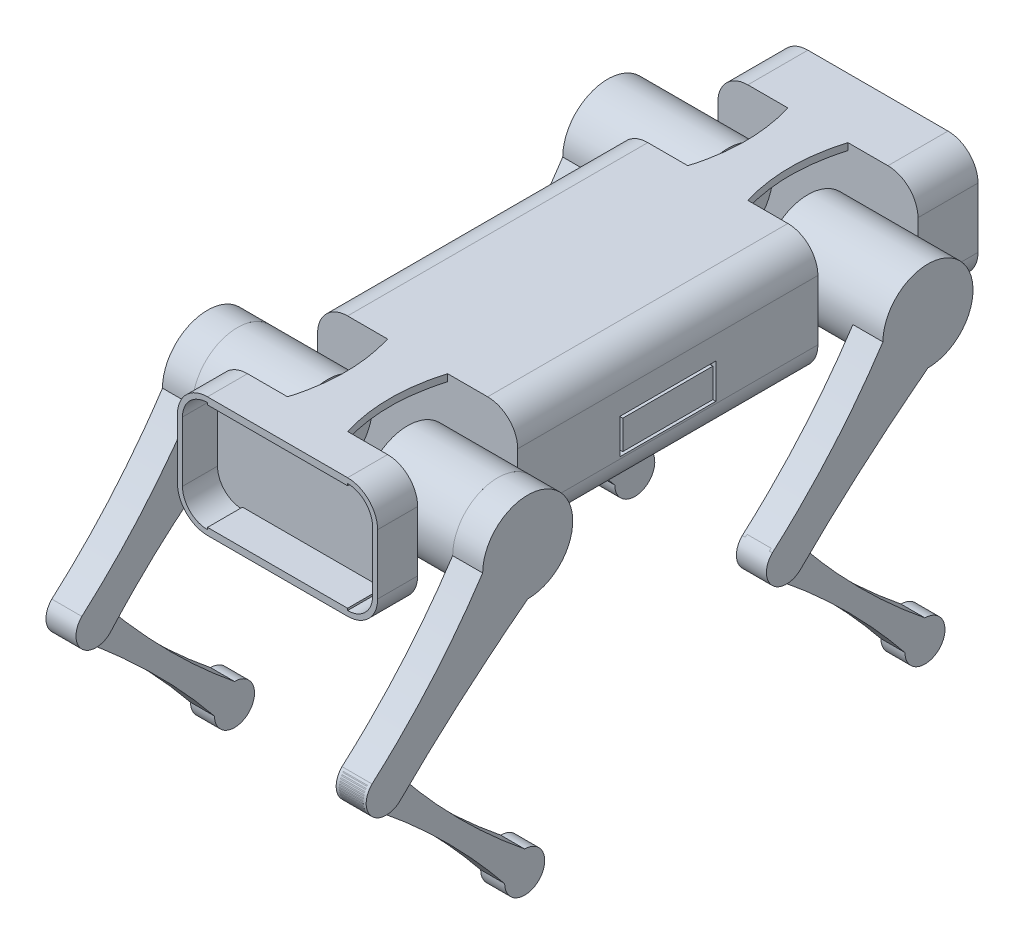
SolidWorks part; units mm, degrees
note: The reader was unsure of these and kept them because the rebuilt part matched: shared geometry of "草图12<2>", "草图13<2>".
ref_plane "前视基准面" through (0, 0, 0) normal (0, 0, 1) x (1, 0, 0)
ref_plane "上视基准面" through (0, 0, 0) normal (0, 1, 0) x (1, 0, 0)
ref_plane "右视基准面" through (0, 0, 0) normal (1, 0, 0) x (0, 0, -1)
sketch "草图1" plane through (0, 0, 0) normal (0, 0, 1) x (1, 0, 0)
  line L0 (-100, 30) -> (-100, -30)
  line L1 (-70, -60) -> (70, -60)
  line L6 (100, 30) -> (100, -30)
  line L7 (70, 60) -> (-70, 60)
  arc A0 (-70, 60) -> (-100, 30) centre (-70, 30) ccw
  arc A1 (-70, -60) -> (-100, -30) centre (-70, -30) cw
  arc A2 (100, -30) -> (70, -60) centre (70, -30) cw
  arc A3 (100, 30) -> (70, 60) centre (70, 30) ccw
extrude "机身" add sketch "草图1" along normal blind 300
ref_plane "基准面4" through (0, 0, 0) normal (-1, 0, 0) x (0, 0, 1)
sketch "草图3" plane through (0, 0, 0) normal (-1, 0, 0) x (0, 0, 1)
  circle A0 centre (-50, 0) radius 45
  circle A2 centre (350, 0) radius 45
extrude "髋部" add sketch "草图3" along normal mid plane 260 separate body
sketch "草图6" plane through (0, 0, 0) normal (-1, 0, 0) x (0, 0, 1)
  circle A0 centre (-50, 0) radius 45
  circle A1 centre (350, 0) radius 45
extrude "髋部切1" cut sketch "草图6" against normal mid plane 80
ref_plane "基准面5" through (-130, 0, 0) normal (-1, 0, 0) x (0, 0, 1)
sketch "草图7" plane through (-130, 0, 0) normal (-1, 0, 0) x (0, 0, 1)
  circle A0 centre (-50, 0) radius 45 construction
  arc A1 (77.2792, -155.5635) -> (105.5635, -127.2792) centre (91.4214, -141.4214) ccw
  arc A2 (-50, -45) -> (-5, 0) centre (-50, 0) cw
  arc A5 (477.2792, -155.5635) -> (505.5635, -127.2792) centre (491.4214, -141.4214) ccw [skipped]
  arc A6 (350, -45) -> (395, 0) centre (350, 0) cw [skipped]
  arc A7 (477.2792, -155.5635) -> (505.5635, -127.2792) centre (491.4214, -141.4214) ccw
  arc A8 (350, -45) -> (395, 0) centre (350, 0) cw
  spline S0 degree 2 poles (-50, -45) (21.0347, -91.8313) (77.2792, -155.5635) knots 0 0 0 1 1 1
  spline S1 degree 2 poles (-5, 0) (41.8313, -71.0347) (105.5635, -127.2792) knots 0 0 0 1 1 1
  spline S2 degree 2 poles (350, -45) (421.0347, -91.8313) (477.2792, -155.5635) knots 0 0 0 1 1 1
  spline S3 degree 2 poles (395, 0) (441.8313, -71.0347) (505.5635, -127.2792) knots 0 0 0 1 1 1
  dimension "D1" = 2
extrude "左大腿" add sketch "草图7" along normal blind 30
ref_plane "基准面6" through (130, 0, 0) normal (1, 0, 0) x (0, 0, -1)
sketch "草图8" plane through (130, 0, 0) normal (1, 0, 0) x (0, 0, -1)
  line L0 (-350, -45) -> (-420.8207, -99.105) construction
  line L1 (-420.8207, -99.105) -> (-477.2792, -155.5635) construction
  line L3 (50, -45) -> (-20.8207, -99.105) construction
  line L4 (-20.8207, -99.105) -> (-77.2792, -155.5635) construction
  arc A5 (-395, 0) -> (-350, -45) centre (-350, 0) cw
  arc A6 (-477.2792, -155.5635) -> (-505.5635, -127.2792) centre (-491.4214, -141.4214) cw
  arc A9 (5, 0) -> (50, -45) centre (50, 0) cw
  circle A10 centre (50, 0) radius 45 construction
  arc A11 (-77.2792, -155.5635) -> (-105.5635, -127.2792) centre (-91.4214, -141.4214) cw
  parabola Q0 (-105.5635, -127.2792) -> (5, 0) focus (-285.6819, 139.285) apex (-47.5776, -69.0817) construction
  spline S0 degree 2 poles (50, -45) (-20.8207, -99.105) (-77.2792, -155.5635) knots 0 0 0 1 1 1
  spline S1 degree 2 poles (5, 0) (-41.8313, -71.0347) (-105.5635, -127.2792) knots 0 0 0 1 1 1
  spline S2 degree 2 poles (-350, -45) (-420.8207, -99.105) (-477.2792, -155.5635) knots 0 0 0 1 1 1
  spline S3 degree 2 poles (-395, 0) (-441.8313, -71.0347) (-505.5635, -127.2792) knots 0 0 0 1 1 1
  dimension "D1" = 2
extrude "右大腿" add sketch "草图8" along normal blind 30
ref_plane "基准面7" through (0, 60, 0) normal (0, 1, 0) x (1, 0, 0)
sketch "草图10" plane through (0, 60, 0) normal (0, 1, 0) x (1, 0, 0)
  line L1 (70, 100) -> (30, 100)
  line L7 (70, -400) -> (70, -440)
  line L9 (70, -400) -> (30, -400)
  line L12 (30, -400) -> (15, -350) construction
  line L13 (15, -350) -> (30, -300) construction
  line L14 (-30, -400) -> (-15, -350) construction
  line L15 (-15, -350) -> (-30, -300) construction
  line L16 (30, -300) -> (-30, -300)
  line L19 (70, 0) -> (-70, 0) construction
  line L20 (-30, 0) -> (30, 0)
  line L25 (-70, 160) -> (-70, 100)
  line L26 (70, 160) -> (70, 100)
  line L27 (-30, 100) -> (-15, 50) construction
  line L28 (-15, 50) -> (-30, 0) construction
  line L29 (30, 100) -> (15, 50) construction
  line L30 (15, 50) -> (30, 0) construction
  line L31 (-30, 100) -> (-70, 100)
  line L32 (-70, 160) -> (70, 160)
  line L33 (70, -440) -> (-70, -440)
  line L34 (-30, -400) -> (-70, -400)
  line L35 (-70, -400) -> (-70, -440)
  spline S0 degree 2 poles (30, -400) (15, -350) (30, -300) knots 0 0 0 1 1 1
  spline S1 degree 2 poles (-30, -400) (-15, -350) (-30, -300) knots 0 0 0 1 1 1
  spline S2 degree 2 poles (-30, 100) (-15, 50) (-30, 0) knots 0 0 0 1 1 1
  spline S3 degree 2 poles (30, 100) (15, 50) (30, 0) knots 0 0 0 1 1 1
extrude "上机架" add sketch "草图10" against normal blind 7 separate body
ref_plane "基准面8" through (0, -60, 0) normal (0, -1, 0) x (-1, 0, 0)
sketch "草图11" plane through (0, -60, 0) normal (0, -1, 0) x (-1, 0, 0)
  line L0 (-30, 100) -> (-70, 100)
  line L1 (-70, 100) -> (-70, 160)
  line L2 (-70, 160) -> (70, 160)
  line L3 (70, 160) -> (70, 100)
  line L4 (70, 100) -> (30, 100)
  line L5 (-70, -440) -> (70, -440)
  line L6 (70, -440) -> (70, -400)
  line L7 (70, -400) -> (30, -400)
  line L8 (-30, 100) -> (-11.25, 50) construction
  line L9 (-11.25, 50) -> (-30, 0) construction
  line L12 (30, 100) -> (11.25, 50) construction
  line L13 (11.25, 50) -> (30, 0) construction
  line L16 (-30, 0) -> (30, 0)
  line L17 (-30, -400) -> (-70, -400)
  line L18 (-70, -400) -> (-70, -440)
  line L24 (-30, -300) -> (-11.25, -350) construction
  line L25 (-11.25, -350) -> (-30, -400) construction
  line L28 (30, -300) -> (11.25, -350) construction
  line L29 (11.25, -350) -> (30, -400) construction
  line L30 (-30, -300) -> (30, -300)
  spline S0 degree 2 poles (-30, 100) (-11.25, 50) (-30, 0) knots 0 0 0 1 1 1
  spline S1 degree 2 poles (30, 100) (11.25, 50) (30, 0) knots 0 0 0 1 1 1
  spline S2 degree 2 poles (-30, -300) (-11.25, -350) (-30, -400) knots 0 0 0 1 1 1
  spline S3 degree 2 poles (30, -300) (11.25, -350) (30, -400) knots 0 0 0 1 1 1
extrude "下机架" add sketch "草图11" against normal blind 7
ref_plane "基准面9" through (0, 0, -100) normal (0, 0, 1) x (1, 0, 0)
sketch "草图12" plane through (0, 0, -100) normal (0, 0, 1) x (1, 0, 0)
  line L0 (-70, -60) -> (70, -60)
  line L1 (-77, -60) -> (77, -60) construction
  line L3 (70, 60) -> (-70, 60)
  line L4 (70, 60) -> (-70, 60) construction
  line L5 (77, 60) -> (-77, 60) construction
  line L7 (-100, 30) -> (-100, -30)
  line L9 (100, 30) -> (100, -30)
  arc A0 (-100, -30) -> (-70, -60) centre (-70, -30) ccw construction
  arc A1 (70, -60) -> (100, -30) centre (70, -30) ccw construction
  arc A2 (70, -60) -> (100, -30) centre (70, -30) ccw
  arc A3 (70, 60) -> (100, 30) centre (70, 30) cw
  arc A4 (100, 30) -> (70, 60) centre (70, 30) ccw construction
  arc A5 (-70, 60) -> (-100, 30) centre (-70, 30) ccw
  arc A6 (-70, 60) -> (-100, 30) centre (-70, 30) ccw construction
  arc A7 (-70, -60) -> (-100, -30) centre (-70, -30) cw
extrude "头" add sketch "草图12" against normal blind 5
extrude "头框" add sketch "草图12<2>" against normal blind 60 thin thin type one direction reverse wall 5
sketch "草图12<2>" plane through (0, 0, -100) normal (0, 0, 1) x (1, 0, 0) same geometry as "草图12"
ref_plane "基准面10" through (0, 0, 400) normal (0, 0, -1) x (-1, 0, 0)
sketch "草图13" plane through (0, 0, 400) normal (0, 0, -1) x (-1, 0, 0)
  line L0 (70, -60) -> (-70, -60)
  line L3 (70, 60) -> (-70, 60)
  line L4 (-70, 53) -> (-70, 60) construction
  line L7 (100, 30) -> (100, -30)
  line L8 (-100, 30) -> (-100, -30)
  arc A0 (-70, 60) -> (-100, 30) centre (-70, 30) ccw construction
  arc A1 (70, 60) -> (100, 30) centre (70, 30) cw
  arc A2 (100, 30) -> (70, 60) centre (70, 30) ccw construction
  arc A3 (70, -60) -> (100, -30) centre (70, -30) ccw
  arc A4 (70, -60) -> (100, -30) centre (70, -30) ccw construction
  arc A5 (-70, 60) -> (-100, 30) centre (-70, 30) ccw
  arc A6 (-70, -60) -> (-100, -30) centre (-70, -30) cw
  arc A7 (-100, -30) -> (-70, -60) centre (-70, -30) ccw construction
extrude "尾" add sketch "草图13" against normal blind 5
extrude "尾框" add sketch "草图13<2>" against normal blind 40 thin
sketch "草图13<2>" plane through (0, 0, 400) normal (0, 0, -1) x (-1, 0, 0) same geometry as "草图13"
sketch "草图14" plane through (-130, 0, 0) normal (-1, 0, 0) x (0, 0, 1)
  line L0 (370, -282.8427) -> (424.2462, -215.6676) construction
  line L1 (-30, -282.8427) -> (24.2462, -215.6676) construction
  line L2 (24.2462, -215.6676) -> (102.028, -152.028) construction
  line L3 (80.8148, -130.8148) -> (17.1751, -208.5965) construction
  line L4 (17.1751, -208.5965) -> (-50, -262.8427) construction
  line L5 (424.2462, -215.6676) -> (502.028, -152.028) construction
  line L6 (480.8148, -130.8148) -> (417.1751, -208.5965) construction
  line L7 (417.1751, -208.5965) -> (350, -262.8427) construction
  arc A1 (80.8148, -130.8148) -> (102.028, -152.028) centre (91.4214, -141.4214) cw
  arc A3 (480.8148, -130.8148) -> (502.028, -152.028) centre (491.4214, -141.4214) cw
  arc A4 (-50, -262.8427) -> (-30, -282.8427) centre (-50, -282.8427) ccw
  arc A5 (350, -262.8427) -> (370, -282.8427) centre (350, -282.8427) ccw
  spline S0 degree 2 poles (-30, -282.8427) (24.2462, -215.6676) (102.028, -152.028) knots 0 0 0 1 1 1
  spline S1 degree 2 poles (80.8148, -130.8148) (17.1751, -208.5965) (-50, -262.8427) knots 0 0 0 1 1 1
  spline S2 degree 2 poles (370, -282.8427) (424.2462, -215.6676) (502.028, -152.028) knots 0 0 0 1 1 1
  spline S3 degree 2 poles (480.8148, -130.8148) (417.1751, -208.5965) (350, -262.8427) knots 0 0 0 1 1 1
extrude "左小腿" add sketch "草图14" along normal blind 24 from offset 3
sketch "草图15" plane through (0, -60, 0) normal (0, -1, 0) x (-1, 0, 0)
  line L1 (-55, 100) -> (55, 100) construction
  line L3 (-15, 0) -> (-15, 100)
  line L4 (-15, 100) -> (15, 100)
  line L5 (15, 100) -> (15.6503, 0)
  line L6 (15.6503, 0) -> (-15, 0)
  line L8 (15, -300) -> (15, -400)
  line L9 (55, -400) -> (-55, -400) construction
  line L10 (15, -400) -> (-15, -400)
  line L11 (-15, -400) -> (-15, -300)
  line L12 (-15, -300) -> (15, -300)
extrude "腹部摄像" add sketch "草图15" along normal blind 5 thin thin type one direction wall 5
sketch "草图16" plane through (130, 0, 0) normal (1, 0, 0) x (0, 0, -1)
  line L0 (-491.4214, -161.4214) -> (-424.2462, -215.6676) construction
  line L1 (-424.2462, -215.6676) -> (-370, -282.8427) construction
  line L2 (-471.4214, -141.4214) -> (-417.1751, -208.5965) construction
  line L3 (-91.4214, -161.4214) -> (-24.2462, -215.6676) construction
  line L4 (-24.2462, -215.6676) -> (30, -282.8427) construction
  line L5 (-71.4214, -141.4214) -> (-17.1751, -208.5965) construction
  line L6 (-17.1751, -208.5965) -> (50, -262.8427) construction
  line L7 (-417.1751, -208.5965) -> (-350, -262.8427) construction
  arc A0 (-91.4214, -161.4214) -> (-71.4214, -141.4214) centre (-91.4214, -141.4214) cw
  arc A2 (50, -262.8427) -> (30, -282.8427) centre (50, -282.8427) cw
  arc A3 (30, -282.8427) -> (50, -262.8427) centre (50, -282.8427) ccw construction
  arc A4 (-105.5635, -127.2792) -> (-77.2792, -155.5635) centre (-91.4214, -141.4214) ccw construction
  arc A6 (-491.4214, -161.4214) -> (-471.4214, -141.4214) centre (-491.4214, -141.4214) cw
  arc A7 (-350, -262.8427) -> (-370, -282.8427) centre (-350, -282.8427) cw
  parabola Q0 (-68.4075, -145.7159) -> (50, -262.8427) focus (343.0267, -152.1227) apex (308.3936, -382.6702) construction
  spline S0 degree 2 poles (-91.4214, -161.4214) (-24.2462, -215.6676) (30, -282.8427) knots 0 0 0 1 1 1
  spline S1 degree 2 poles (-71.4214, -141.4214) (-17.1751, -208.5965) (50, -262.8427) knots 0 0 0 1 1 1
  spline S2 degree 2 poles (-491.4214, -161.4214) (-424.2462, -215.6676) (-370, -282.8427) knots 0 0 0 1 1 1
  spline S3 degree 2 poles (-471.4214, -141.4214) (-417.1751, -208.5965) (-350, -262.8427) knots 0 0 0 1 1 1
extrude "右小腿" add sketch "草图16" along normal blind 24 from offset 3
ref_plane "基准面11" through (-100, 0, 0) normal (-1, 0, 0) x (0, 0, 1)
sketch "草图17" plane through (-100, 0, 0) normal (-1, 0, 0) x (0, 0, 1)
  line L0 (105, 4) -> (105, -26)
  line L4 (105, 4) -> (195, 4)
  line L6 (105, -26) -> (195, -26)
  line L7 (195, 4) -> (195, -26)
extrude "切除-拉伸-薄壁2" cut sketch "草图17" against normal blind 5 thin
ref_plane "基准面12" through (100, 0, 0) normal (1, 0, 0) x (0, 0, -1)
sketch "草图18" plane through (100, 0, 0) normal (1, 0, 0) x (0, 0, -1)
  line L3 (-195, 4) -> (-105, 4)
  line L4 (-105, 4) -> (-105, -24.9604)
  line L5 (-105, -24.9604) -> (-195, -24.9604)
  line L6 (-195, -24.9604) -> (-195, 4)
extrude "切除-拉伸-薄壁4" cut sketch "草图18" against normal blind 5 thin thin type one direction wall 3
